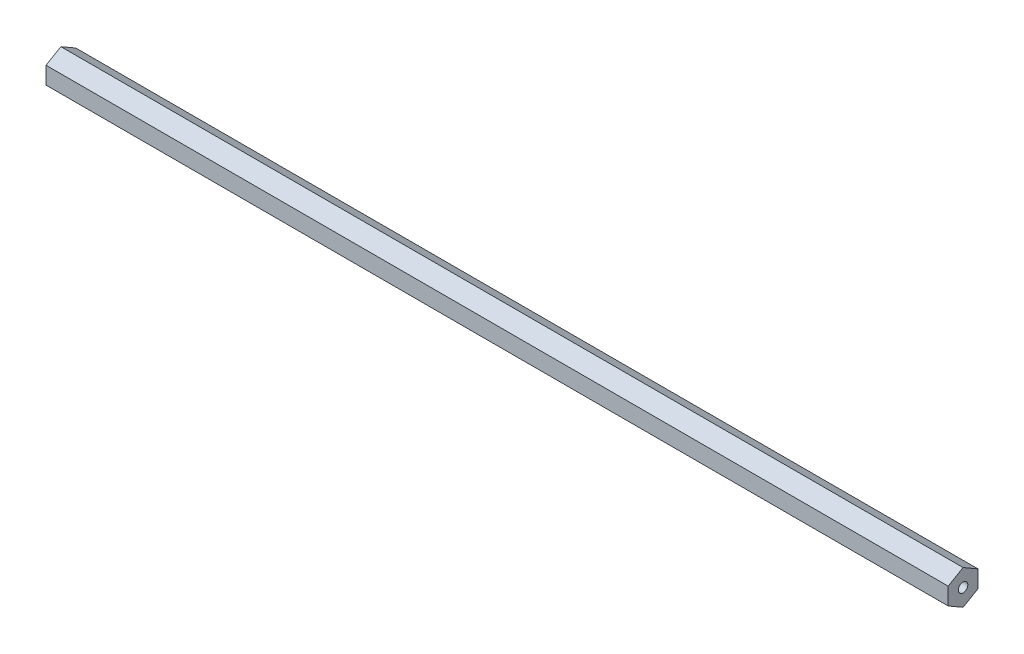
SolidWorks part; units mm, degrees
material "7075-T6 (SN)"
ref_plane "Front Plane" through (0, 0, 0) normal (0, 0, 1) x (1, 0, 0)
ref_plane "Top Plane" through (0, 0, 0) normal (0, 1, 0) x (1, 0, 0)
ref_plane "Right Plane" through (0, 0, 0) normal (1, 0, 0) x (0, 0, -1)
sketch "Sketch1" plane through (0, 0, 0) normal (1, 0, 0) x (0, 0, -1)
  line L1 (0, 7.3323) -> (-6.35, 3.6662)
  line L2 (-6.35, 3.6662) -> (-6.35, -3.6662)
  line L3 (-6.35, -3.6662) -> (0, -7.3323)
  line L4 (0, -7.3323) -> (6.35, -3.6662)
  line L5 (6.35, -3.6662) -> (6.35, 3.6662)
  line L6 (6.35, 3.6662) -> (0, 7.3323)
  circle A2 centre (0, 0) radius 6.35 construction
  dimension "D2" = 12.7
extrude "Boss-Extrude1" add sketch "Sketch1" along normal mid plane 384.175 contours L5 L6 L1 L2 L3 L4 region at (0, 0, 0)
hole_wizard "#10-32 Tapped Hole2" positions "3DSketch2" profile "Sketch5" tap size "#10-32" standard "ANSI Inch"
sketch3d "3DSketch2"
  point P0 (192.0875, 0, 0)
  point P12 (-192.0875, 0, 0)
sketch "Sketch5" plane through (192.0875, 0, 0) normal (0, 1, 0) x (0, 0, -1)
  line L0 (0, 0) -> (0, 17.5608)
  line L1 (0, 17.5608) -> (2.0193, 16.3474)
  line L2 (2.0193, 16.3474) -> (2.0193, 0)
  line L5 (2.0193, 0) -> (0, 0)
  line L10 (0, 17.5608) -> (-2.0193, 16.3474) construction
  line L11 (0, -6.35) -> (0, 107.95) construction
  dimension "Tap Drill Dia." = 4.0386
  dimension "Tap Drill Depth" = 16.3474
  dimension "Drill Angle" = 118
cosmetic thread "Hole Thread3" parameters "D1"=13.97, "D2"=4.826
cosmetic thread "Hole Thread4" parameters "D1"=13.97, "D2"=4.826
